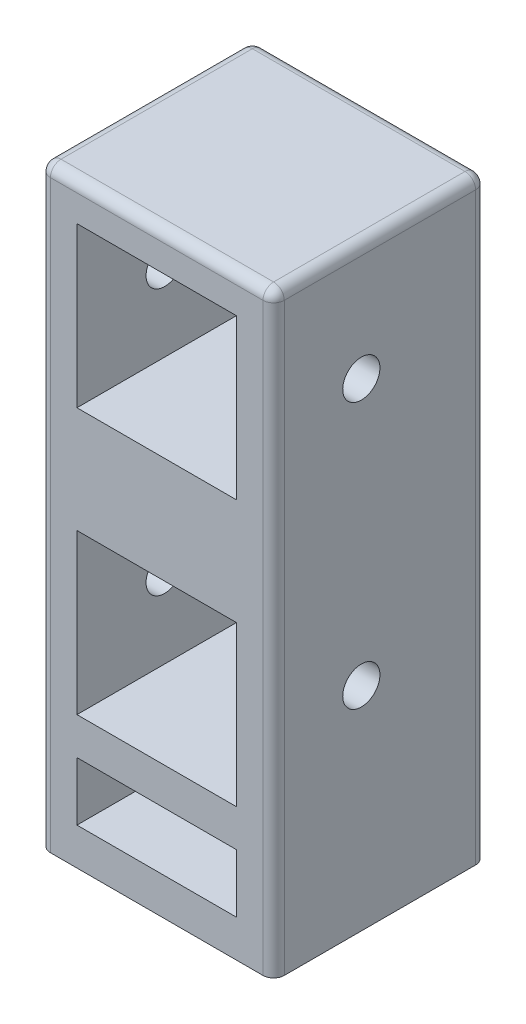
SolidWorks part; units mm, degrees
ref_plane "Front Plane" through (0, 0, 0) normal (0, 0, 1) x (1, 0, 0)
ref_plane "Top Plane" through (0, 0, 0) normal (0, 1, 0) x (1, 0, 0)
ref_plane "Right Plane" through (0, 0, 0) normal (1, 0, 0) x (0, 0, -1)
sketch "Sketch1" plane through (0, 0, 0) normal (0, 0, 1) x (1, 0, 0)
  line L1 (-25.0962, 42.3339) -> (-3.0962, 42.3339)
  line L2 (-25.0962, 42.3339) -> (-25.0962, -13.6661)
  line L3 (-25.0962, -13.6661) -> (-3.0962, -13.6661)
  line L4 (-3.0962, 42.3339) -> (-3.0962, -13.6661)
  line L5 (-21.5962, 38.8339) -> (-6.5962, 38.8339)
  line L6 (-21.5962, 38.8339) -> (-21.5962, 23.8339)
  line L7 (-21.5962, 23.8339) -> (-6.5962, 23.8339)
  line L8 (-6.5962, 38.8339) -> (-6.5962, 23.8339)
  dimension "D1" = 22
  dimension "D2" = 56
  dimension "D3" = 15
  dimension "D4" = 3.5
  dimension "D5" = 3.5
  dimension "D6" = 15
extrude "Boss-Extrude1" add sketch "Sketch1" along normal blind 20
sketch "Sketch2" plane through (0, 0, 20) normal (0, 0, 1) x (1, 0, 0)
  line L0 (-3.0962, -13.6661) -> (-3.0962, 42.3339) construction
  line L1 (-21.5962, 13.8339) -> (-6.5962, 13.8339)
  line L2 (-21.5962, 13.8339) -> (-21.5962, -1.1661)
  line L3 (-21.5962, -1.1661) -> (-6.5962, -1.1661)
  line L4 (-6.5962, 13.8339) -> (-6.5962, -1.1661)
  line L5 (-21.5962, 23.8339) -> (-6.5962, 23.8339) construction
  line L6 (-25.0962, -13.6661) -> (-3.0962, -13.6661) construction
  line L7 (-21.5962, -4.6661) -> (-6.5962, -4.6661)
  line L8 (-21.5962, -4.6661) -> (-21.5962, -10.1661)
  line L9 (-21.5962, -10.1661) -> (-6.5962, -10.1661)
  line L10 (-6.5962, -4.6661) -> (-6.5962, -10.1661)
  dimension "D1" = 15
  dimension "D2" = 3.5
  dimension "D3" = 10
  dimension "D4" = 15
  dimension "D5" = 15
  dimension "D6" = 3.5
  dimension "D7" = 3.5
extrude "Cut-Extrude1" cut sketch "Sketch2" against normal offset from surface (15.5 mm away) 4.5 up to face at (-14.0962, 14.3339, 0)
fillet "Fillet1" radius 1 8 edges at (-14.0962, 42.3339, 0) (-14.0962, 42.3339, 20) (-3.0962, 42.3339, 10) (-3.0962, 14.3339, 0) (-3.0962, 14.3339, 20) (-25.0962, 14.3339, 0) (-25.0962, 14.3339, 20) (-25.0962, 42.3339, 10)
sketch "Sketch3" plane through (-25.0962, 0, 0) normal (-1, 0, 0) x (0, 0, 1)
  line L0 (11.75, -13.6661) -> (11.75, 43.4795) construction
  line L1 (19, -13.6661) -> (1, -13.6661) construction
  line L2 (20, 41.3339) -> (20, -13.6661) construction
  line L3 (20, 38.8339) -> (0, 38.8339) construction
  line L4 (4.5, 13.8339) -> (20, 13.8339) construction
  circle A0 centre (11.75, 31.3339) radius 1.75
  circle A1 centre (11.75, 6.3339) radius 1.75
  dimension "D2" = 3.5
  dimension "D3" = 7.5
  dimension "D4" = 7.5
  dimension "D1" = 8.25
extrude "Cut-Extrude2" cut sketch "Sketch3" against normal blind 35
